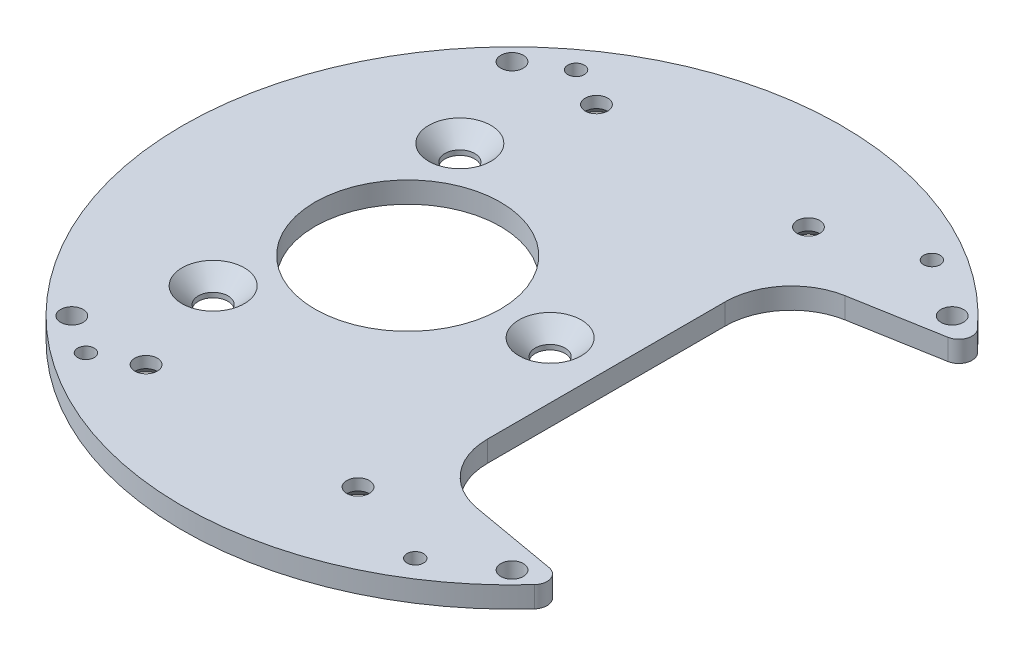
SolidWorks part; units mm, degrees
ref_plane "Front" through (0, 0, 0) normal (0, 0, 1) x (1, 0, 0)
ref_plane "Top" through (0, 0, 0) normal (0, 1, 0) x (1, 0, 0)
ref_plane "Right" through (0, 0, 0) normal (1, 0, 0) x (0, 0, -1)
sketch "Sketch1" plane through (0, 0, 0) normal (0, 1, 0) x (1, 0, 0)
  circle A0 centre (0, 0) radius 49.75
  dimension "D1" = 99.5
extrude "Boss-Extrude1" add sketch "Sketch1" along normal blind 3.175
sketch "Sketch2" plane through (0, 3.175, 0) normal (0, 1, 0) x (1, 0, 0)
  line L0 (0, 0) -> (-15.75, 0) construction
  line L1 (14.25, 26.3268) -> (14.25, -26.3268)
  line L2 (0, 0) -> (33.2269, 33.2269) construction
  line L3 (0, 0) -> (49.75, 0) construction
  line L4 (14.25, 26.3268) -> (39.1364, 30.7149)
  line L5 (14.25, -26.3268) -> (39.1364, -30.7149)
  circle A0 centre (-15.75, 0) radius 30 construction
  circle A2 centre (0, 0) radius 49.75 construction
  arc A3 (39.1364, 30.7149) -> (39.1364, -30.7149) centre (0, 0) cw
  circle A4 centre (33.2269, 33.2269) radius 3.5
  point P6 (14.25, 0)
  circle M5 centre (0, 0) radius 49.75
  dimension "D2" = 60
  dimension "D4" = 7
  dimension "D1" = 15.75
  dimension "D3" = 45
  dimension "D5" = 100
  dimension "D6" = 46.99
extrude "Cut-Extrude1" cut sketch "Sketch2" against normal through all contours L1 M5 region at (30.9281, 3.175, 0)
sketch "Sketch3" plane through (0, 3.175, 0) normal (0, 1, 0) x (1, 0, 0)
  circle A0 centre (-15.75, 0) radius 14
  dimension "D1" = 28
extrude "Cut-Extrude2" cut sketch "Sketch3" against normal through all
sketch "Sketch4" plane through (0, 3.175, 0) normal (0, 1, 0) x (1, 0, 0)
  line L0 (-15.75, 0) -> (5.75, 0) construction
  line L1 (-15.75, 0) -> (0, 0) construction
  dimension "D1" = 21.5
  dimension "D2" = 0
hole_wizard "CSK for M4 Flat Head Machine Screw1" positions "Sketch5" profile "Sketch6" countersink size "M4" standard "ANSI Metric" end condition through all
sketch "Sketch5" plane through (0, 3.175, 0) normal (0, 1, 0) x (1, 0, 0)
  point P0 (5.75, 0)
sketch "Sketch6" plane through (5.75, 3.175, 0) normal (1, 0, 0) x (0, 0, 1)
  line L0 (0, 0) -> (0, 3.175)
  line L1 (0, 3.175) -> (2.25, 3.175)
  line L2 (2.25, 3.175) -> (2.25, 2.45)
  line L3 (2.25, 2.45) -> (4.7, 0)
  line L5 (4.7, 0) -> (0, 0)
  line L6 (-2.25, 2.45) -> (-4.7, 0) construction
  line L11 (0, -6.35) -> (0, 107.95) construction
  dimension "Thru Hole Dia." = 4.5
  dimension "Thru Hole Depth" = 3.175
  dimension "Near C'Sink Dia." = 9.4
  dimension "Near C'Sink Angle" = 90
ref_axis "Axis1" through (-15.75, 3.175, 0) along (0, 1, 0)
pattern_circular "CirPattern1" count 3 over 360 about axis through (-15.75, 3.175, 0) along (0, 1, 0) of "CSK for M4 Flat Head Machine Screw1"
sketch "Sketch7" plane through (0, 3.175, 0) normal (0, 1, 0) x (1, 0, 0)
  line L0 (0, 0) -> (33.2269, 33.2269) construction
  line L1 (0, 0) -> (63.0088, 0) construction
  dimension "D1" = 46.99
  dimension "D2" = 45
hole_wizard "Ø3.4 (3.4) Diameter Hole1" positions "Sketch8" profile "Sketch9" hole size "Ø3.4" standard "ANSI Metric" end condition through all
sketch "Sketch8" plane through (0, 0, 0) normal (0, -1, 0) x (-1, 0, 0)
  point P0 (-33.2269, 33.2269)
sketch "Sketch9" plane through (33.2269, 0, -33.2269) normal (1, 0, 0) x (0, 0, -1)
  line L0 (0, 0) -> (0, 3.175)
  line L1 (0, 3.175) -> (1.7, 3.175)
  line L2 (1.7, 3.175) -> (1.7, 0)
  line L5 (1.7, 0) -> (0, 0)
  line L11 (0, -6.35) -> (0, 107.95) construction
  dimension "Thru Hole Dia." = 3.4
  dimension "Thru Hole Depth" = 3.175
ref_axis "Axis2" through (0, 3.175, 0) along (0, -1, 0)
pattern_circular "CirPattern2" count 4 over 360 about axis through (0, 3.175, 0) along (0, -1, 0) of "Ø3.4 (3.4) Diameter Hole1" reverse direction yes
sketch "Sketch11" plane through (0, 0, 0) normal (0, -1, 0) x (1, 0, 0)
  line L0 (14.25, 0) -> (-5.25, 0) construction
  line L1 (14.25, -26.3268) -> (14.25, 26.3268) construction
  line L3 (-21.25, -34) -> (10.75, -34) construction
  line L4 (-21.25, -34) -> (-21.25, 34) construction
  line L5 (-21.25, 34) -> (10.75, 34) construction
  line L6 (10.75, -34) -> (10.75, 34) construction
  line L7 (-21.25, -34) -> (10.75, 34) construction
  line L8 (-21.25, 34) -> (10.75, -34) construction
  dimension "D1" = 32
  dimension "D2" = 68
  dimension "D3" = 3.5
hole_wizard "CSK for M3 Flat Head Machine Screw2" positions "Sketch12" profile "Sketch13" countersink size "M3" standard "ANSI Metric" end condition through all
sketch "Sketch12" plane through (0, 0, 0) normal (0, -1, 0) x (-1, 0, 0)
  point P0 (21.25, -34)
  point P3 (-10.75, -34)
  point P6 (-10.75, 34)
  point P9 (21.25, 34)
sketch "Sketch13" plane through (-21.25, 0, 34) normal (1, 0, 0) x (0, 0, -1)
  line L0 (0, 0) -> (0, 3.175)
  line L1 (0, 3.175) -> (1.7, 3.175)
  line L2 (1.7, 3.175) -> (1.7, 1.45)
  line L3 (1.7, 1.45) -> (3.15, 0)
  line L5 (3.15, 0) -> (0, 0)
  line L6 (-1.7, 1.45) -> (-3.15, 0) construction
  line L11 (0, -6.35) -> (0, 107.95) construction
  dimension "Thru Hole Dia." = 3.4
  dimension "Thru Hole Depth" = 3.175
  dimension "Near C'Sink Dia." = 6.3
  dimension "Near C'Sink Angle" = 90
fillet "Fillet1" radius 2 2 edges at (39.1364, 1.5875, 30.7149) (39.1364, 1.5875, -30.7149)
fillet "Fillet2" radius 10 2 edges at (14.25, 1.5875, -26.3268) (14.25, 1.5875, 26.3268)
sketch "Sketch14" plane through (0, 3.175, 0) normal (0, 1, 0) x (1, 0, 0)
  arc A0 (24.3926, 39) -> (-27.3313, 37) centre (0, 0) ccw
  arc A1 (-27.3313, -37) -> (24.3926, -39) centre (0, 0) ccw
  dimension "D1" = 46
  dimension "D2" = 74
  dimension "D3" = 78
hole_wizard "M3x0.5 Tapped Hole1" positions "Sketch15" profile "Sketch16" tap size "M3x0.5" standard "ANSI Metric" end condition through all
sketch "Sketch15" plane through (0, 3.175, 0) normal (0, 1, 0) x (1, 0, 0)
  point P0 (-27.3313, -37)
  point P3 (24.3926, -39)
  point P6 (24.3926, 39)
  point P9 (-27.3313, 37)
sketch "Sketch16" plane through (-27.3313, 3.175, 37) normal (1, 0, 0) x (0, 0, 1)
  line L0 (0, 0) -> (0, 3.175)
  line L1 (0, 3.175) -> (1.25, 3.175)
  line L2 (1.25, 3.175) -> (1.25, 0)
  line L5 (1.25, 0) -> (0, 0)
  line L11 (0, -6.35) -> (0, 107.95) construction
  dimension "Thru Tap Drill Dia." = 2.5
  dimension "Thru Tap Drill Depth" = 3.175
cosmetic thread "Hole Thread1" parameters "D2"=3
cosmetic thread "Hole Thread2" parameters "D2"=3
cosmetic thread "Hole Thread3" parameters "D2"=3
cosmetic thread "Hole Thread4" parameters "D2"=3
sketch "Sketch17" plane through (0, 3.175, 0) normal (0, 1, 0) x (1, 0, 0)
  circle A0 centre (-33.2269, -33.2269) radius 2.75
  circle A1 centre (33.2269, -33.2269) radius 2.75
  circle A2 centre (-33.2269, 33.2269) radius 2.75
  circle A3 centre (33.2269, 33.2269) radius 2.75
  dimension "D1" = 5.5
